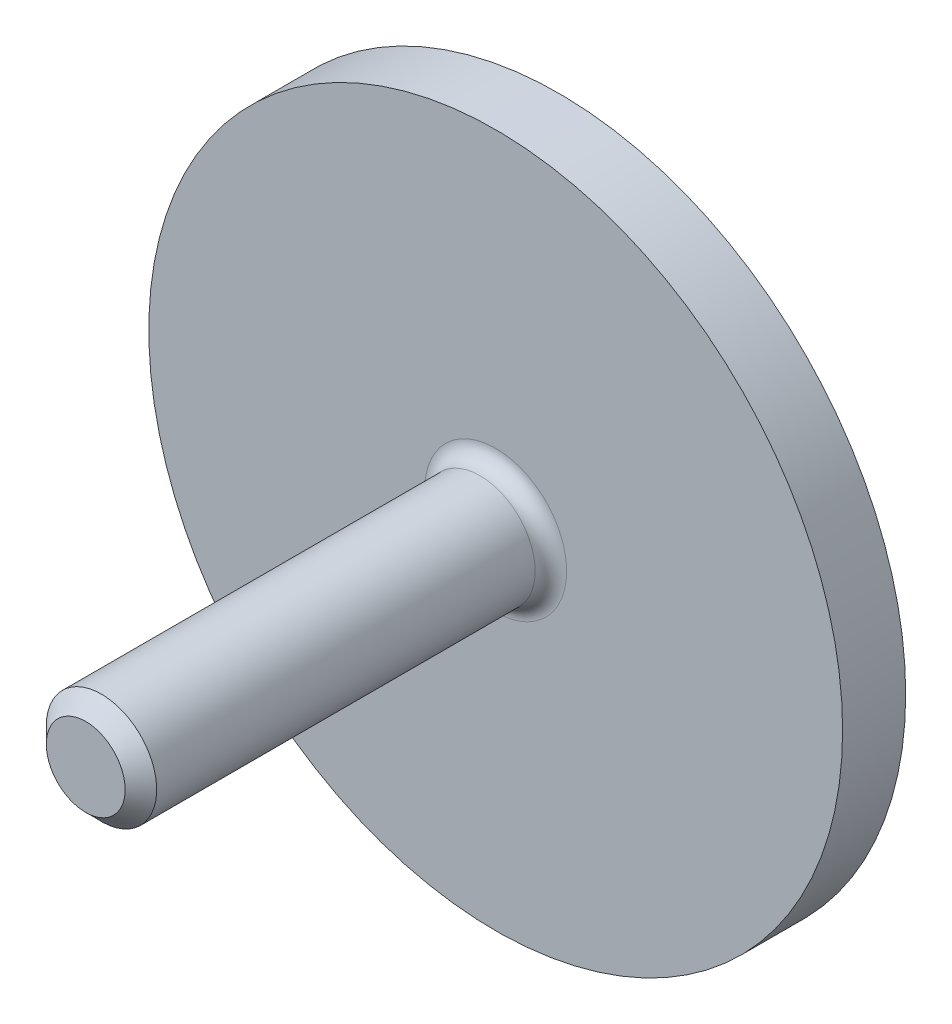
SolidWorks part; units mm, degrees
note: '?' marks a value the reader was unsure of.
ref_plane "Face" through (0, 0, 0) normal (0, 0, 1) x (1, 0, 0)
ref_plane "Dessus" through (0, 0, 0) normal (0, 1, 0) x (1, 0, 0)
ref_plane "Droite" through (0, 0, 0) normal (1, 0, 0) x (0, 0, -1)
ref_axis "Axe1" through (0, 0, -50) along (0, 0, 1)?
sketch "Esquisse1" plane through (0, 0, 0) normal (0, 0, 1) x (1, 0, 0)
  circle A0 centre (0, 0) radius 11
  circle A1 centre (0, 0) radius 11 construction
extrude "Base-Extrusion" add sketch "Esquisse1" along normal blind 2
sketch "Esquisse3" plane through (0, 0, 2) normal (0, 0, 1) x (1, 0, 0)
  circle A0 centre (0, 0) radius 1.75
  dimension "D1" = 3.5
extrude "Boss.-Extru.1" add sketch "Esquisse3" along normal blind 13
chamfer "Chanfrein1" distance 0.5 angle 45 1 edges at (1.75, 0, 15)
fillet "Congé1" radius 0.5 1 edges at (1.75, 0, 2)
